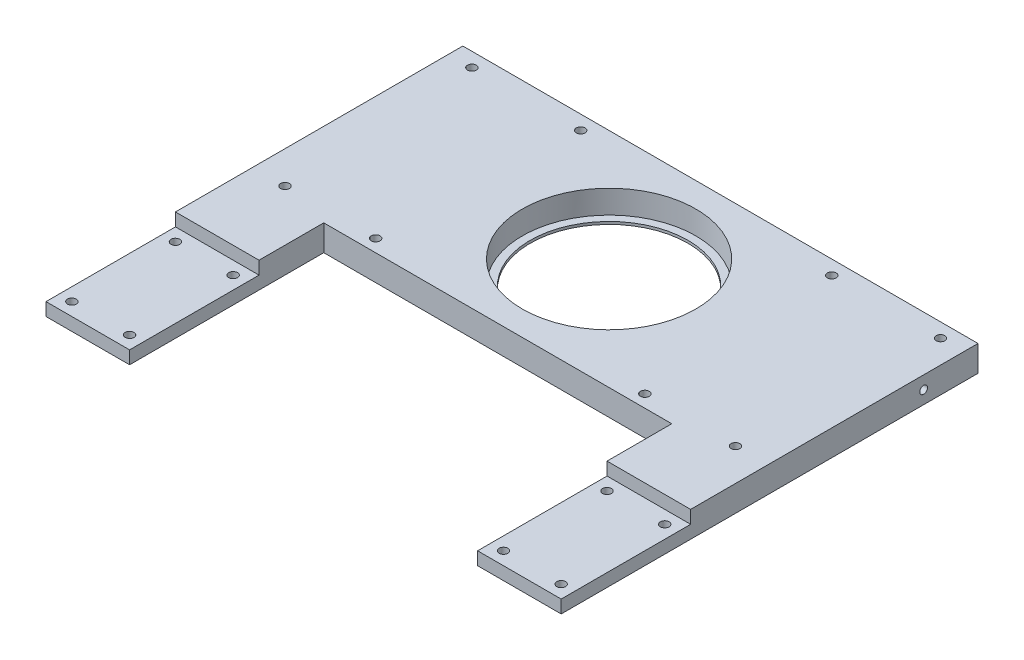
SolidWorks part; units mm, degrees
ref_plane "Ebene vorne" through (0, 0, 0) normal (0, 0, 1) x (1, 0, 0)
ref_plane "Ebene oben" through (0, 0, 0) normal (0, 1, 0) x (1, 0, 0)
ref_plane "Ebene rechts" through (0, 0, 0) normal (1, 0, 0) x (0, 0, -1)
sketch "Skizze1" plane through (0, 0, 0) normal (0, 1, 0) x (1, 0, 0)
  line L1 (-99.5, -200) -> (99.5, -200)
  line L2 (-99.5, -200) -> (-99.5, 200)
  line L3 (-99.5, 200) -> (99.5, 200)
  line L4 (99.5, -200) -> (99.5, 200)
  line L5 (-99.5, -200) -> (99.5, 200) construction
  line L6 (-99.5, 200) -> (99.5, -200) construction
  point P0 (0, 0)
  dimension "D1" = 199
  dimension "D2" = 400
extrude "Aufsatz-Linear austragen1" add sketch "Skizze1" along normal blind 10
ref_plane "Ebene1" through (0, -92.6125, 77.7111) normal (0, -0.766, 0.6428) x (1, 0, 0)
sketch "Skizze2" plane through (0, -92.6125, 77.7111) normal (0, -0.766, 0.6428) x (1, 0, 0)
  line L1 (-99.5, 159.6368) -> (99.5, 159.6368) construction
  circle A0 centre (0, 139.6368) radius 5
  dimension "D1" = 10
  dimension "D2" = 20
extrude "Schnitt-Linear austragen1" [suppressed] cut sketch "Skizze2" against normal blind 30 and the other way blind 10
sketch "Skizze3" [suppressed] plane through (0, -67.9923, 57.0523) normal (0, -0.766, 0.6428) x (1, 0, 0)
  circle A0 centre (0, 101.3345) radius 5
  dimension "D1" = 10
extrude "Aufsatz-Linear austragen2" [suppressed] add sketch "Skizze3" along normal blind 0.1
sketch "Skizze4" plane through (0, -92.6125, 77.7111) normal (0, -0.766, 0.6428) x (1, 0, 0)
  line L0 (0, 159.6368) -> (0, 159.9002) construction
  line L1 (-99.5, 159.6368) -> (99.5, 159.6368) construction
  line L2 (-25, 159.6368) -> (-25, 194.6368)
  line L3 (-25, 194.6368) -> (25, 194.6368)
  line L4 (-25, 159.6368) -> (25, 159.6368)
  line L5 (25, 159.6368) -> (25, 194.6368)
  point P10 (0, 194.6368)
  dimension "D1" = 50
  dimension "D2" = 35
extrude "Aufsatz-Linear austragen3" [suppressed] add sketch "Skizze4" against normal blind 10 separate body
sketch "Skizze5" plane through (0, 10, 0) normal (0, 1, 0) x (1, 0, 0)
  line L0 (0, 0) -> (0, -200) construction
  line L1 (-99.5, -200) -> (99.5, -200) construction
  line L2 (99.5, -200) -> (18, -200)
  line L3 (-18, -200) -> (-99.5, -46)
  line L4 (-99.5, 200) -> (-99.5, -200) construction
  line L5 (-99.5, -46) -> (-99.5, -200)
  line L6 (-99.5, -200) -> (-18, -200)
  line L7 (99.5, -46) -> (99.5, -200)
  line L8 (18, -200) -> (99.5, -46)
  line L9 (-99.5, 200) -> (-99.5, 115)
  line L10 (-99.5, 115) -> (99.5, 115)
  line L11 (99.5, -200) -> (99.5, 200) construction
  line L12 (99.5, 115) -> (99.5, 200)
  line L13 (99.5, 200) -> (-99.5, 200)
  line L14 (67.211, -46) -> (-67.211, -46)
  line L15 (-67.211, -46) -> (-2.6461, -168)
  line L16 (67.211, -46) -> (2.6461, -168)
  line L17 (-2.6461, -168) -> (2.6461, -168)
  line L18 (2.6461, -168) -> (0, -173) construction
  line L19 (-2.6461, -168) -> (0, -173) construction
  point P27 (0, -46)
  dimension "D1" = 36
  dimension "D2" = 154
  dimension "D3" = 85
  dimension "D4" = 32
  dimension "D5" = 27
extrude "Schnitt-Linear austragen2" cut sketch "Skizze5" against normal blind 10
sketch "Skizze6" plane through (0, 10, 0) normal (0, 1, 0) x (1, 0, 0)
  line L0 (0, -200) -> (0, -168) construction
  line L1 (-18, -200) -> (18, -200) construction
  line L2 (-2.6461, -168) -> (2.6461, -168) construction
  line L3 (0, -186.59) -> (-21.075, -186.59) construction
  circle A0 centre (-11, -195) radius 1.7
  circle A1 centre (-11, -178.18) radius 1.7
  circle A2 centre (11, -195) radius 1.7
  circle A3 centre (11, -178.18) radius 1.7
  dimension "D1" = 3.4
  dimension "D2" = 11
  dimension "D3" = 5
  dimension "D4" = 13.41
extrude "Schnitt-Linear austragen3" cut sketch "Skizze6" against normal through all
sketch "Skizze7" plane through (0, 0, 0) normal (0, -1, 0) x (1, 0, 0)
  line L0 (-11, 195) -> (-11, 200) construction
  line L1 (-18, 200) -> (18, 200) construction
  line L2 (-11, 195) -> (-5.1092, 195) construction
  line L3 (-11, 198.4064) -> (-8.05, 196.7032)
  line L4 (-8.05, 196.7032) -> (-8.05, 193.2968)
  line L5 (-11, 191.5936) -> (-8.05, 193.2968)
  line L6 (-11, 191.5936) -> (-13.95, 193.2968)
  line L7 (-13.95, 196.7032) -> (-13.95, 193.2968)
  line L8 (-11, 198.4064) -> (-13.95, 196.7032)
  line L9 (0, 200) -> (0, 121.6034) construction
  line L10 (11, 195) -> (11, 178.18) construction
  line L11 (11, 186.59) -> (0, 186.59) construction
  line L12 (11, 198.4064) -> (8.05, 196.7032)
  line L13 (11, 191.5936) -> (8.05, 193.2968)
  line L14 (8.05, 196.7032) -> (8.05, 193.2968)
  line L15 (11, 191.5936) -> (13.95, 193.2968)
  line L16 (13.95, 196.7032) -> (13.95, 193.2968)
  line L17 (11, 198.4064) -> (13.95, 196.7032)
  line L18 (-8.05, 176.4768) -> (-8.05, 179.8832)
  line L19 (-11, 181.5864) -> (-13.95, 179.8832)
  line L20 (-11, 181.5864) -> (-8.05, 179.8832)
  line L21 (-13.95, 176.4768) -> (-13.95, 179.8832)
  line L22 (-11, 174.7736) -> (-13.95, 176.4768)
  line L23 (-11, 174.7736) -> (-8.05, 176.4768)
  line L24 (8.05, 176.4768) -> (8.05, 179.8832)
  line L25 (11, 181.5864) -> (8.05, 179.8832)
  line L26 (11, 181.5864) -> (13.95, 179.8832)
  line L27 (13.95, 176.4768) -> (13.95, 179.8832)
  line L28 (11, 174.7736) -> (13.95, 176.4768)
  line L29 (11, 174.7736) -> (8.05, 176.4768)
  point P10 (-8.05, 195)
  dimension "D1" = 120
  dimension "D2" = 5.9
extrude "Schnitt-Linear austragen4" cut sketch "Skizze7" against normal blind 4
sketch "Skizze8" plane through (0, 10, 0) normal (0, 1, 0) x (1, 0, 0)
  line L0 (99.5, 105.41) -> (78.872, 105.41) construction
  line L1 (99.5, -46) -> (99.5, 115) construction
  line L2 (-99.5, 115) -> (99.5, 115) construction
  dimension "D1" = 9.59
ref_plane "Ebene2" through (0, 57.7725, -48.4769) normal (0, 0.766, -0.6428) x (-1, 0, 0)
sketch "Skizze9" plane through (0, 57.7725, -48.4769) normal (0, 0.766, -0.6428) x (-1, 0, 0)
  line L0 (-99.5, -74.3209) -> (-78.872, -74.3209) construction
  line L1 (-99.5, 41.6659) -> (-99.5, -81.6672) construction
  line L2 (0, -45.2589) -> (0, -16.2619) construction
  circle A0 centre (-94.5, -74.3209) radius 1.7
  circle A1 centre (94.5, -74.3209) radius 1.7
  circle A2 centre (-30, -74.3209) radius 1.7
  circle A3 centre (30, -74.3209) radius 1.7
  dimension "D1" = 3.4
  dimension "D2" = 5
  dimension "D3" = 30
extrude "Schnitt-Linear austragen5" [suppressed] cut sketch "Skizze9" against normal through all and the other way through all
ref_plane "Ebene3" through (0, 50.1121, -42.049) normal (0, 0.766, -0.6428) x (-1, 0, 0)
sketch "Skizze10" [suppressed] plane through (0, 55.0361, -46.1808) normal (0, 0.766, -0.6428) x (-1, 0, 0)
  line L0 (-95, -81.9813) -> (-100, -81.9813) construction
  line L1 (-95, -81.9813) -> (-95, -30.0694) construction
  line L2 (-95, -78.7482) -> (-97.8, -80.3647)
  line L3 (-97.8, -80.3647) -> (-97.8, -83.5979)
  line L4 (-95, -85.2145) -> (-97.8, -83.5979)
  line L5 (-95, -85.2145) -> (-92.2, -83.5979)
  line L6 (-92.2, -80.3647) -> (-92.2, -83.5979)
  line L7 (-95, -78.7482) -> (-92.2, -80.3647)
  line L8 (0, 0) -> (0, -45.6283) construction
  line L9 (-30, -81.9813) -> (-95, -81.9813) construction
  line L10 (-62.5, -81.9813) -> (-62.5, -23.1343) construction
  line L11 (-32.8, -80.3647) -> (-32.8, -83.5979)
  line L12 (-30, -85.2145) -> (-32.8, -83.5979)
  line L13 (-30, -85.2145) -> (-27.2, -83.5979)
  line L14 (-27.2, -80.3647) -> (-27.2, -83.5979)
  line L15 (-30, -78.7482) -> (-27.2, -80.3647)
  line L16 (-30, -78.7482) -> (-32.8, -80.3647)
  line L17 (95, -78.7482) -> (92.2, -80.3647)
  line L18 (92.2, -80.3647) -> (92.2, -83.5979)
  line L19 (95, -85.2145) -> (92.2, -83.5979)
  line L20 (95, -85.2145) -> (97.8, -83.5979)
  line L21 (97.8, -80.3647) -> (97.8, -83.5979)
  line L22 (95, -78.7482) -> (97.8, -80.3647)
  line L23 (30, -78.7482) -> (32.8, -80.3647)
  line L24 (30, -78.7482) -> (27.2, -80.3647)
  line L25 (27.2, -80.3647) -> (27.2, -83.5979)
  line L26 (30, -85.2145) -> (27.2, -83.5979)
  line L27 (30, -85.2145) -> (32.8, -83.5979)
  line L28 (32.8, -80.3647) -> (32.8, -83.5979)
  point P9 (-97.8, -81.9813)
  point P31 (97.8, -81.9813)
  dimension "D1" = 120
  dimension "D2" = 5.6
extrude "Schnitt-Linear austragen6" [suppressed] cut sketch "Skizze10" against normal blind 10 and the other way blind 5
sketch "Skizze13" plane through (0, 10, 0) normal (0, 1, 0) x (1, 0, 0)
  line L0 (67.211, -46) -> (99.5, -46) construction
  line L1 (67.211, -46) -> (92.4353, -59.3492) construction
  line L2 (99.5, -46) -> (18, -200) construction
  line L3 (0, 0) -> (0, -38.1435) construction
  line L4 (2.6461, -168) -> (67.211, -46) construction
  line L5 (79.8232, -52.6746) -> (99.764, -14.995) construction
  line L6 (99.5, -46) -> (99.5, 115) construction
  line L7 (83.3555, -46) -> (83.3555, -1) construction
  line L8 (93.5, -48.8065) -> (96.9981, -42.1965) construction
  line L9 (83.1285, -76.935) -> (57.9043, -63.5858) construction
  line L10 (71.7911, -70.935) -> (86.3039, -70.935) construction
  circle A0 centre (93.5, -48.8065) radius 1.7
  circle A1 centre (72.5142, -48.8065) radius 1.7
  circle A2 centre (81.7891, -70.935) radius 1.7
  circle A3 centre (-81.7891, -70.935) radius 1.7
  circle A4 centre (-93.5, -48.8065) radius 1.7
  circle A5 centre (-72.5142, -48.8065) radius 1.7
  dimension "D1" = 6
  dimension "D5" = 35
  dimension "D3" = 3.4
  dimension "D6" = 3.4
  dimension "D2" = 6
  dimension "D4" = 6
extrude "Schnitt-Linear austragen7" [suppressed] cut sketch "Skizze13" against normal through all
sketch "Skizze14" plane through (96.7476, 0, 51.2008) normal (0.8839, 0, 0.4678) x (0.4678, 0, -0.8839)
  line L0 (-29.1157, 5) -> (-29.1157, 10)
  line L5 (5.8843, 0) -> (5.8843, 10) construction
  line L6 (-29.1157, 5) -> (5.8843, 5)
  line L7 (5.8843, 10) -> (-168.3519, 10) construction
  line L8 (-29.1157, 10) -> (5.8843, 10)
  line L9 (5.8843, 10) -> (5.8843, 5)
  dimension "D1" = 35
extrude "Schnitt-Linear austragen8" [suppressed] cut sketch "Skizze14" against normal up to surface (28.9525 mm away)
mirror "Spiegeln1" [suppressed] about plane through (0, 0, 0) normal (1, 0, 0)
sketch "Skizze15" [suppressed] plane through (95, 0, 0) normal (1, 0, 0) x (0, 0, -1)
  line L0 (4, 10) -> (4, 0)
  line L1 (4, 0) -> (65, 0)
  line L2 (65, 0) -> (65, 10)
  line L3 (65, 10) -> (4, 10)
extrude "Schnitt-Linear austragen9" [suppressed] cut sketch "Skizze15" against normal through all
sketch "Skizze16" plane through (0, 0, 0) normal (0, -1, 0) x (1, 0, 0)
  line L0 (0, 200) -> (0, 168) construction
  line L1 (-18, 200) -> (18, 200) construction
  line L2 (-2.6461, 168) -> (2.6461, 168) construction
  line L3 (11, 186.59) -> (0, 186.59) construction
  line L4 (11, 195) -> (11, 178.18) construction
  line L6 (-17.5, 183.09) -> (17.5, 183.09)
  line L7 (-17.5, 183.09) -> (-17.5, 190.09)
  line L8 (-17.5, 190.09) -> (17.5, 190.09)
  line L9 (17.5, 183.09) -> (17.5, 190.09)
  line L10 (-17.5, 183.09) -> (17.5, 190.09) construction
  line L11 (-17.5, 190.09) -> (17.5, 183.09) construction
  dimension "D1" = 7
  dimension "D2" = 35
extrude "Schnitt-Linear austragen10" cut sketch "Skizze16" against normal blind 5
sketch "Skizze17" plane through (17.5, 0, 0) normal (-1, 0, 0) x (0, 0, 1)
  line L0 (186.59, 0) -> (186.59, 11.1261) construction
  line L1 (183.09, 0) -> (190.09, 0) construction
  line L2 (183.09, 5) -> (186.59, 8.5)
  line L3 (186.59, 8.5) -> (190.09, 5)
  line L4 (190.09, 5) -> (183.09, 5)
  dimension "D1" = 90
extrude "Schnitt-Linear austragen11" cut sketch "Skizze17" along normal up to surface (35 mm away) up to face at (-17.5, 2.5, 186.59)
sketch "Skizze18" [suppressed] plane through (0, 10, 0) normal (0, 1, 0) x (1, 0, 0)
  line L0 (0, -210) -> (0, 0) construction
  line L1 (-18, -210) -> (18, -210) construction
  line L2 (62.5765, -72.2325) -> (35.4483, -67.5372)
  line L3 (15.3378, -155.8503) -> (-22.1774, -134.6566)
  line L4 (2.8247, -178) -> (62.5765, -72.2325) construction
  line L5 (-15.3378, -155.8503) -> (22.1774, -134.6566)
  line L6 (58.6594, -79.166) -> (40.7308, -76.063)
  line L7 (0, -147.1854) -> (19.5429, -147.1854) construction
  line L8 (0, -95.4) -> (31.4297, -95.4) construction
  line L9 (11.6488, -162.3803) -> (0, -155.7995)
  line L10 (-71.7468, -56) -> (-2.8247, -178) construction
  line L11 (0, -95.4) -> (-37.5153, -116.5937) construction
  line L12 (-37.5153, -116.5937) -> (-39.2566, -117.5774) construction
  line L13 (-11.6488, -162.3803) -> (0, -155.7995)
  line L14 (-58.6594, -79.166) -> (-40.7308, -76.063)
  line L15 (-62.5765, -72.2325) -> (-35.4483, -67.5372)
  circle A0 centre (0, -95.4) radius 33.5
  arc A1 (7.4594, -151.3994) -> (7.4594, -142.9713) centre (9.84, -147.1854) cw
  arc A2 (-7.4594, -151.3994) -> (-7.4594, -142.9713) centre (-9.84, -147.1854) ccw
  circle A3 centre (0, -95.4) radius 45.0879
  point P17 (0, -147.1854)
  point P36 (5, -147.1854)
  point P40 (-5, -147.1854)
  line M16 (62.5765, -72.2325) -> (2.8247, -178)
  line M18 (-2.8247, -178) -> (-71.7468, -56)
  dimension "D2" = 67
  dimension "D5" = 2
  dimension "D4" = 10
  dimension "D1" = 114.6
  dimension "D3" = 7.5
  dimension "D6" = 7.5
extrude "Aufsatz-Linear austragen4" [suppressed] add sketch "Skizze18" against normal blind 10 contours A3 L15 L14 M18 | A3 A0 M16 M18 | A3 L6 L2 M16 | A2 L5 L3 | A3 L3 L5 | L3 A1 L5 | L13 L9 L3 L5 M18 M16
sketch "Skizze19" [suppressed] plane through (0, 0, 0) normal (0, -1, 0) x (1, 0, 0)
  circle A0 centre (0, 35.4) radius 31.5
  circle A1 centre (0, 35.4) radius 33.5
  circle A2 centre (0, 35.4) radius 33.5 construction
  dimension "D1" = 63
extrude "Aufsatz-Linear austragen5" [suppressed] add sketch "Skizze19" against normal blind 1
sketch "Skizze20" plane through (0, 10, 0) normal (0, 1, 0) x (1, 0, 0)
  line L0 (99.5, 109.52) -> (55.4083, 109.52) construction
  line L1 (99.5, -46) -> (99.5, 115) construction
  line L2 (-99.5, 115) -> (99.5, 115) construction
  line L3 (0, 115) -> (0, 96.9732) construction
  line L4 (105, 33.82) -> (35.5869, 33.82) construction
  circle A0 centre (90.5, 109.52) radius 1.7
  circle A1 centre (48.5, 109.52) radius 1.7
  circle A2 centre (-48.5, 109.52) radius 1.7
  circle A3 centre (-90.5, 109.52) radius 1.7
  circle A4 centre (87, 33.82) radius 1.7
  circle A5 centre (52, 33.82) radius 1.7
  circle A6 centre (-87, 33.82) radius 1.7
  circle A7 centre (-52, 33.82) radius 1.7
  dimension "D1" = 3.4
  dimension "D2" = 5.48
  dimension "D3" = 9
  dimension "D4" = 42
  dimension "D5" = 75.7
  dimension "D6" = 12.5
  dimension "D7" = 35
extrude "Schnitt-Linear austragen12" cut sketch "Skizze20" against normal through all
sketch "Skizze21" plane through (0, 10, 0) normal (0, 1, 0) x (1, 0, 0)
  line L0 (-67.211, -46) -> (-67.211, 29)
  line L1 (-67.211, 29) -> (67.211, 29)
  line L2 (67.211, 29) -> (67.211, -46)
  line L3 (67.211, -46) -> (-67.211, -46) construction
  line L4 (-67.211, -46) -> (67.211, -46)
  dimension "D1" = 75
extrude "Schnitt-Linear austragen13" cut sketch "Skizze21" against normal through all
sketch "Skizze22" plane through (0, 10, 0) normal (0, 1, 0) x (1, 0, 0)
  line L0 (-67.211, -46) -> (-2.6461, -168)
  arc A0 (-67.211, -46) -> (-2.6461, -168) centre (60.0769, -56.7211) ccw
  line M19 (-2.6461, -168) -> (-67.211, -46)
extrude "Schnitt-Linear austragen14" cut sketch "Skizze22" against normal through all contours M19 region at (-42.1385, 10, 110.8156)
sketch "Skizze23" plane through (0, 10, 0) normal (0, 1, 0) x (1, 0, 0)
  line L0 (-18, -200) -> (-99.5, -46) construction
  line L1 (-99.5, -46) -> (-18, -200)
  arc A0 (-18, -200) -> (-99.5, -46) centre (114.4449, -31.3416) cw
  arc A2 (-67.211, -46) -> (-2.6461, -168) centre (60.0769, -56.7211) ccw construction
  dimension "D1" = 60
extrude "Aufsatz-Linear austragen6" add sketch "Skizze23" against normal blind 10
mirror "Spiegeln2" about plane through (0, 0, 0) normal (1, 0, 0) of "Aufsatz-Linear austragen6", "Schnitt-Linear austragen14"
sketch "Skizze25" plane through (0, 10, 0) normal (0, 1, 0) x (1, 0, 0)
  line L0 (-99.5, -46) -> (-67.211, -46) construction
  line L1 (-99.5, 4) -> (-99.5, -46) construction
  line L2 (-99.5, 4) -> (-67.211, 4) construction
  line L3 (-67.211, 29) -> (-67.211, -46) construction
  line L4 (-83.3555, 4) -> (-83.3555, -46) construction
  line L5 (-99.5, -21) -> (-67.211, -21) construction
  line L6 (-99.5, 115) -> (-99.5, -46) construction
  circle A0 centre (-94.5, -1) radius 1.7
  circle A1 centre (-72.211, -1) radius 1.7
  circle A2 centre (-72.211, -41) radius 1.7
  circle A3 centre (-94.5, -41) radius 1.7
  dimension "D2" = 3.4
  dimension "D1" = 50
  dimension "D3" = 5
  dimension "D4" = 5
extrude "Schnitt-Linear austragen15" cut sketch "Skizze25" against normal through all
sketch "Skizze26" plane through (-99.5, 0, 0) normal (-1, 0, 0) x (0, 0, 1)
  line L0 (-4, 5) -> (-4, 13.1015)
  line L1 (46, 0) -> (46, 10) construction
  line L2 (46, 5) -> (-4, 5)
  line L4 (-115, 0) -> (46, 0) construction
  line L5 (46, 5) -> (46, 0)
  line L6 (-4, 13.1015) -> (200.6846, 82.5463)
  line L7 (200.6846, 82.5463) -> (242.9972, -41.0376)
  line L8 (242.9972, -41.0376) -> (91.2415, -60.2848)
  line L9 (91.2415, -60.2848) -> (46, 0)
  dimension "D1" = 50
mirror "Spiegeln3" about plane through (0, 0, 0) normal (1, 0, 0) of "Schnitt-Linear austragen15"
extrude "Schnitt-Linear austragen16" cut sketch "Skizze26" against normal through all
sketch "Skizze27" plane through (0, 10, 0) normal (0, 1, 0) x (1, 0, 0)
  line L0 (0, 29) -> (0, 115) construction
  line L1 (67.211, 29) -> (-67.211, 29) construction
  line L2 (-99.5, 115) -> (99.5, 115) construction
  circle A0 centre (0, 72) radius 33.5
  dimension "D1" = 67
extrude "Schnitt-Linear austragen17" cut sketch "Skizze27" against normal through all
sketch "Skizze28" plane through (0, 0, 0) normal (0, -1, 0) x (1, 0, 0)
  circle A0 centre (0, -72) radius 30.5
  circle A1 centre (0, -72) radius 33.5 construction
  circle A2 centre (0, -72) radius 36.0063
  dimension "D1" = 3
extrude "Aufsatz-Linear austragen7" add sketch "Skizze28" against normal blind 1
sketch "Skizze29" plane through (-99.5, 0, 0) normal (-1, 0, 0) x (0, 0, 1)
  line L0 (-115, 5) -> (-93.4233, 5) construction
  line L1 (-115, 0) -> (-115, 10) construction
  circle A0 centre (-94, 5) radius 1.5
  dimension "D1" = 3
  dimension "D2" = 21
extrude "Schnitt-Linear austragen18" cut sketch "Skizze29" against normal blind 10
sketch "Skizze30" plane through (0, 0, -115) normal (0, 0, -1) x (-1, 0, 0)
  line L0 (99.5, 5) -> (60.2539, 5) construction
  line L1 (99.5, 0) -> (99.5, 10) construction
  circle A0 centre (94.5, 5) radius 1.5
  circle A1 centre (78.5, 5) radius 1.5
  dimension "D1" = 3
  dimension "D2" = 5
  dimension "D3" = 21
extrude "Schnitt-Linear austragen19" cut sketch "Skizze30" against normal blind 10
mirror "Spiegeln4" about plane through (0, 0, 0) normal (1, 0, 0) of "Schnitt-Linear austragen18", "Schnitt-Linear austragen19"
sketch "Skizze31" plane through (0, 0, 0) normal (0, -1, 0) x (1, 0, 0)
  line L0 (0, -115) -> (0, -73.0202) construction
  line L1 (-99.5, -115) -> (99.5, -115) construction
  circle A0 centre (-90.5, -109.52) radius 2.95
  circle A1 centre (-48.5, -109.52) radius 2.95
  circle A2 centre (-87, -33.82) radius 2.95
  circle A3 centre (-52, -33.82) radius 2.95
  circle A4 centre (52, -33.82) radius 2.95
  circle A5 centre (87, -33.82) radius 2.95
  circle A6 centre (48.5, -109.52) radius 2.95
  circle A7 centre (90.5, -109.52) radius 2.95
  dimension "D1" = 5.9
extrude "Schnitt-Linear austragen20" cut sketch "Skizze31" against normal blind 3.5
